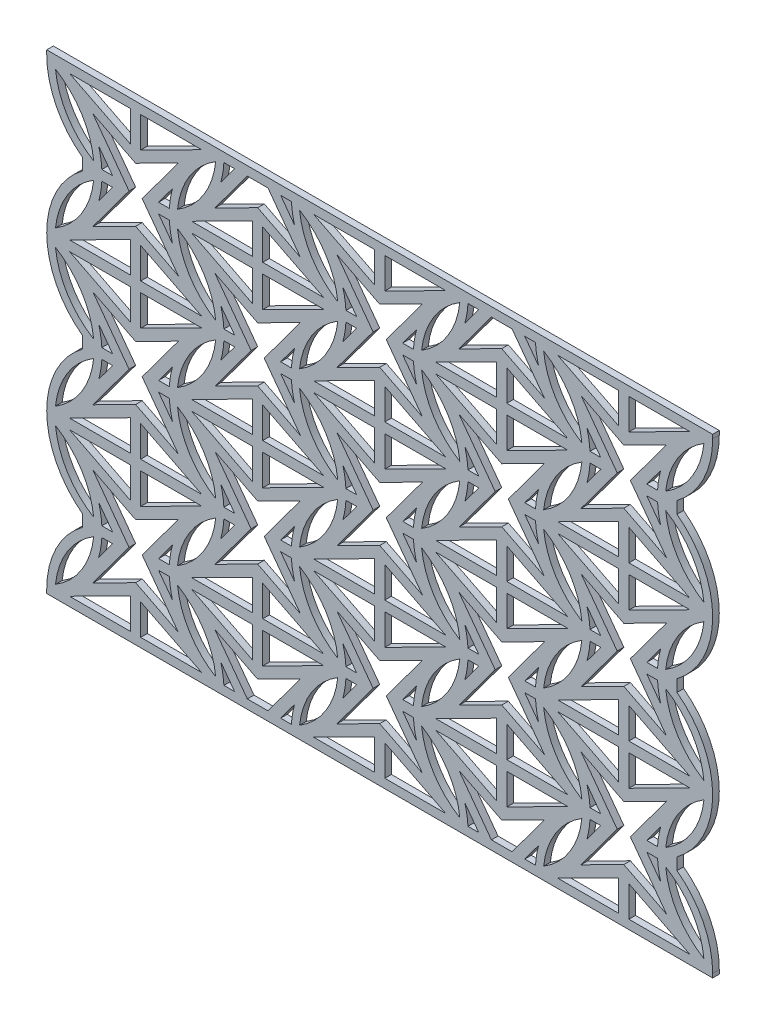
SolidWorks part; units mm, degrees
ref_plane "Front Plane" through (0, 0, 0) normal (0, 0, 1) x (1, 0, 0)
ref_plane "Top Plane" through (0, 0, 0) normal (0, 1, 0) x (1, 0, 0)
ref_plane "Right Plane" through (0, 0, 0) normal (1, 0, 0) x (0, 0, -1)
sketch "Sketch2" plane through (0, 0, 0) normal (0, 0, 1) x (1, 0, 0)
  line L0 (-7.7461, 7.4126) -> (-1.1882, -1.4456)
  line L1 (-0.9234, -14.5032) -> (-11.964, -14.5032)
  line L2 (7.7461, -10.3038) -> (1.1882, -1.4456)
  line L3 (-4.1661, -0.5271) -> (-6.115, -0.5271)
  line L4 (0.9234, 11.4505) -> (0.9234, 11.612)
  line L5 (4.1661, -0.5271) -> (6.115, -0.5271)
  line L6 (-0.9234, 11.612) -> (-11.964, 11.612)
  line L7 (0.9234, -8.927) -> (0.9234, -14.5032)
  line L8 (11.964, 11.612) -> (0.9234, 11.612)
  line L9 (-0.9234, -8.927) -> (-0.9234, -14.3417)
  line L10 (7.7461, 7.4126) -> (1.1882, -1.4456)
  line L11 (0.9234, 6.0358) -> (11.964, 11.612)
  line L12 (-9.6385, -0.3656) -> (-9.6385, -2.5257)
  line L13 (0.9234, -8.927) -> (11.964, -14.5032)
  line L14 (-7.7461, -10.3038) -> (-1.1882, -1.4456)
  line L15 (-4.1661, -2.3642) -> (-6.115, -2.3642)
  line L16 (-0.9234, 6.0358) -> (-11.964, 11.612)
  line L17 (4.1661, -2.3642) -> (6.115, -2.3642)
  line L18 (0, 3.5003) -> (-7.7461, 7.4126)
  line L19 (-16.1, 12.5305) -> (16.1, 12.5305) construction
  line L20 (11.964, -14.5032) -> (0.9234, -14.5032)
  line L21 (0, -6.3916) -> (-7.7461, -10.3038)
  line L22 (-0.9234, 11.4505) -> (-0.9234, 11.612)
  line L23 (-0.9234, -14.3417) -> (-0.9234, -14.5032)
  line L24 (-4.1661, -0.5271) -> (-6.6809, 2.8698)
  line L25 (0.9234, 6.0358) -> (0.9234, 11.4505)
  line L26 (9.6385, -0.3656) -> (9.6385, -2.5257) construction
  line L27 (-0.9234, -8.927) -> (-11.964, -14.5032)
  line L28 (4.1661, -0.5271) -> (6.6809, 2.8698)
  line L29 (4.1661, -2.3642) -> (6.6809, -5.761)
  line L30 (0, -6.3916) -> (7.7461, -10.3038)
  line L31 (-4.1661, -2.3642) -> (-6.6809, -5.761)
  line L32 (-0.9234, 6.0358) -> (-0.9234, 11.4505)
  line L33 (0, 3.5003) -> (7.7461, 7.4126)
  line L34 (-16.1, -15.4218) -> (16.1, -15.4218) construction
  line L35 (-16.1, 12.5305) -> (-16.1, 13.247) construction
  line L36 (-16.1, 13.247) -> (16.1, 13.247) construction
  line L37 (16.1, 13.247) -> (16.1, 12.5305) construction
  line L38 (-16.1, -15.4218) -> (-16.1, -16.1382)
  line L39 (-16.1, -16.1382) -> (16.1, -16.1382)
  line L40 (16.1, -16.1382) -> (16.1, -15.4218) construction
  line L41 (-24.8754, -31.139) -> (-24.8754, -30.9775) construction
  line L42 (-21.6327, -44.9536) -> (-19.6838, -44.9536) construction
  line L43 (-25.7989, -48.981) -> (-18.0527, -52.8933) construction
  line L44 (-41.8989, -30.0589) -> (-41.8989, -29.3425)
  line L45 (-18.0527, -35.1769) -> (-24.6106, -44.0351) construction
  line L46 (-33.545, -52.8933) -> (-26.9871, -44.0351) construction
  line L47 (-9.6989, -29.3425) -> (-9.6989, -30.0589)
  line L48 (-26.7223, -51.5165) -> (-26.7223, -56.9312) construction
  line L49 (-29.965, -44.9536) -> (-31.9139, -44.9536) construction
  line L50 (-41.8989, -58.0112) -> (-41.8989, -58.7277)
  line L51 (-29.965, -43.1165) -> (-32.4798, -39.7197) construction
  line L52 (-41.8989, -58.7277) -> (-9.6989, -58.7277) construction
  line L53 (-33.545, -35.1769) -> (-26.9871, -44.0351) construction
  line L54 (-35.4374, -42.955) -> (-35.4374, -45.1151) construction
  line L55 (-25.7989, -48.981) -> (-33.545, -52.8933) construction
  line L56 (-26.7223, -51.5165) -> (-37.7629, -57.0927) construction
  line L57 (-41.8989, -30.0589) -> (-9.6989, -30.0589) construction
  line L58 (-13.8348, -30.9775) -> (-24.8754, -30.9775) construction
  line L59 (-26.7223, -36.5537) -> (-26.7223, -31.139) construction
  line L60 (-18.0527, -52.8933) -> (-24.6106, -44.0351) construction
  line L61 (-24.8754, -51.5165) -> (-13.8348, -57.0927) construction
  line L62 (-21.6327, -43.1165) -> (-19.1179, -39.7197) construction
  line L63 (-26.7223, -57.0927) -> (-37.7629, -57.0927) construction
  line L64 (-26.7223, -36.5537) -> (-37.7629, -30.9775) construction
  line L65 (-21.6327, -44.9536) -> (-19.1179, -48.3505) construction
  line L66 (-21.6327, -43.1165) -> (-19.6838, -43.1165) construction
  line L67 (-25.7989, -39.0891) -> (-33.545, -35.1769) construction
  line L68 (-29.965, -44.9536) -> (-32.4798, -48.3505) construction
  line L69 (-29.965, -43.1165) -> (-31.9139, -43.1165) construction
  line L70 (-26.7223, -31.139) -> (-26.7223, -30.9775) construction
  line L71 (-41.8989, -29.3425) -> (-9.6989, -29.3425) construction
  line L72 (-26.7223, -30.9775) -> (-37.7629, -30.9775) construction
  line L73 (-26.7223, -56.9312) -> (-26.7223, -57.0927) construction
  line L74 (-9.6989, -58.7277) -> (-9.6989, -58.0112)
  line L75 (-41.8989, -58.0112) -> (-9.6989, -58.0112) construction
  line L76 (-13.8348, -57.0927) -> (-24.8754, -57.0927) construction
  line L77 (-16.1603, -42.955) -> (-16.1603, -45.1151) construction
  line L78 (-24.8754, -51.5165) -> (-24.8754, -57.0927) construction
  line L79 (-24.8754, -36.5537) -> (-24.8754, -31.139) construction
  line L80 (-25.7989, -39.0891) -> (-18.0527, -35.1769) construction
  line L81 (-24.8754, -36.5537) -> (-13.8348, -30.9775) construction
  line L82 (23.0309, -2.5257) -> (23.0309, -2.3642)
  line L83 (26.2736, -16.3403) -> (28.2225, -16.3403) construction
  line L84 (22.1074, -20.3677) -> (29.8536, -24.28) construction
  line L85 (6.0074, -1.4456) -> (6.0074, -0.7292) construction
  line L86 (29.8536, -6.5635) -> (23.9757, -14.5032)
  line L87 (14.3613, -24.28) -> (20.9192, -15.4218) construction
  line L88 (38.2074, -0.7292) -> (38.2074, -1.4456) construction
  line L89 (21.184, -22.9032) -> (21.184, -28.3178) construction
  line L90 (17.9413, -16.3403) -> (15.9924, -16.3403) construction
  line L91 (6.0074, -29.3979) -> (6.0074, -30.1144) construction
  line L92 (17.9413, -14.5032) -> (15.4265, -11.1064)
  line L93 (6.0074, -30.1144) -> (38.2074, -30.1144) construction
  line L94 (14.3613, -6.5635) -> (20.2392, -14.5032)
  line L95 (12.4689, -14.3417) -> (12.4689, -16.5018) construction
  line L96 (22.1074, -20.3677) -> (14.3613, -24.28) construction
  line L97 (21.184, -22.9032) -> (10.1434, -28.4794) construction
  line L98 (6.0074, -1.4456) -> (38.2074, -1.4456) construction
  line L99 (34.0715, -2.3642) -> (23.0309, -2.3642)
  line L100 (21.184, -7.9404) -> (21.184, -2.5257)
  line L101 (29.8536, -24.28) -> (23.2957, -15.4218) construction
  line L102 (23.0309, -22.9032) -> (34.0715, -28.4794) construction
  line L103 (26.2736, -14.5032) -> (28.7884, -11.1064)
  line L104 (21.184, -28.4794) -> (10.1434, -28.4794) construction
  line L105 (21.184, -7.9404) -> (10.1434, -2.3642)
  line L106 (26.2736, -16.3403) -> (28.7884, -19.7372) construction
  line L107 (26.2736, -14.5032) -> (28.2225, -14.5032)
  line L108 (22.1074, -10.4758) -> (14.3613, -6.5635)
  line L109 (17.9413, -16.3403) -> (15.4265, -19.7372) construction
  line L110 (17.9413, -14.5032) -> (15.9924, -14.5032)
  line L111 (21.184, -2.5257) -> (21.184, -2.3642)
  line L112 (6.0074, -0.7292) -> (38.2074, -0.7292) construction
  line L113 (21.184, -2.3642) -> (10.1434, -2.3642)
  line L114 (21.184, -28.3178) -> (21.184, -28.4794) construction
  line L115 (38.2074, -30.1144) -> (38.2074, -29.3979) construction
  line L116 (6.0074, -29.3979) -> (38.2074, -29.3979) construction
  line L117 (34.0715, -28.4794) -> (23.0309, -28.4794) construction
  line L118 (31.746, -14.3417) -> (31.746, -16.5018) construction
  line L119 (23.0309, -22.9032) -> (23.0309, -28.4794) construction
  line L120 (23.0309, -7.9404) -> (23.0309, -2.5257)
  line L121 (22.1074, -10.4758) -> (29.8536, -6.5635)
  line L122 (23.0309, -7.9404) -> (34.0715, -2.3642)
  line L123 (26.2736, 11.612) -> (28.2225, 11.612)
  line L124 (29.8536, 3.6723) -> (23.2957, 12.5305)
  line L125 (23.0309, 5.0491) -> (23.0309, -0.5271)
  line L126 (31.746, 13.6106) -> (31.746, 11.4505) construction
  line L127 (34.0715, 25.5881) -> (23.0309, 25.5881)
  line L128 (38.2074, 27.2231) -> (38.2074, 26.5067) construction
  line L129 (12.4689, 13.6106) -> (12.4689, 11.4505) construction
  line L130 (23.0309, 25.4266) -> (23.0309, 25.5881)
  line L131 (21.184, 5.0491) -> (10.1434, -0.5271)
  line L132 (6.0074, 27.2231) -> (38.2074, 27.2231) construction
  line L133 (23.0309, 5.0491) -> (34.0715, -0.5271)
  line L134 (6.0074, 26.5067) -> (6.0074, 27.2231) construction
  line L135 (6.0074, -1.4456) -> (6.0074, -2.1621) construction
  line L136 (6.0074, -1.4456) -> (38.2074, -1.4456) construction
  line L137 (21.184, 20.0119) -> (10.1434, 25.5881)
  line L138 (23.0309, 20.0119) -> (23.0309, 25.4266)
  line L139 (22.1074, 7.5846) -> (14.3613, 3.6723)
  line L140 (34.0715, -0.5271) -> (23.0309, -0.5271)
  line L141 (17.9413, 13.449) -> (15.9924, 13.449)
  line L142 (23.0309, 20.0119) -> (34.0715, 25.5881)
  line L143 (22.1074, 7.5846) -> (29.8536, 3.6723)
  line L144 (21.184, 20.0119) -> (21.184, 25.4266)
  line L145 (22.1074, 17.4764) -> (29.8536, 21.3887)
  line L146 (26.2736, 13.449) -> (28.2225, 13.449)
  line L147 (17.9413, 13.449) -> (15.4265, 16.8459)
  line L148 (21.184, 25.4266) -> (21.184, 25.5881)
  line L149 (6.0074, 26.5067) -> (38.2074, 26.5067) construction
  line L150 (26.2736, 13.449) -> (28.7884, 16.8459)
  line L151 (38.2074, -2.1621) -> (38.2074, -1.4456) construction
  line L152 (21.184, -0.5271) -> (10.1434, -0.5271)
  line L153 (14.3613, 3.6723) -> (20.9192, 12.5305)
  line L154 (14.3613, 21.3887) -> (20.9192, 12.5305)
  line L155 (21.184, 25.5881) -> (10.1434, 25.5881)
  line L156 (21.184, 5.0491) -> (21.184, -0.3656)
  line L157 (17.9413, 11.612) -> (15.4265, 8.2151)
  line L158 (21.184, -0.3656) -> (21.184, -0.5271)
  line L159 (29.8536, 21.3887) -> (23.2957, 12.5305)
  line L160 (26.2736, 11.612) -> (28.7884, 8.2151)
  line L161 (17.9413, 11.612) -> (15.9924, 11.612)
  line L162 (22.1074, 17.4764) -> (14.3613, 21.3887)
  line L163 (6.0074, -2.1621) -> (38.2074, -2.1621) construction
  line L164 (48.381, -2.3642) -> (50.3299, -2.3642)
  line L165 (51.961, -10.3038) -> (45.4031, -1.4456)
  line L166 (45.1383, -8.927) -> (45.1383, -14.5032)
  line L167 (53.8534, -0.3656) -> (53.8534, -2.5257) construction
  line L168 (56.1789, 11.612) -> (45.1383, 11.612)
  line L169 (60.3149, 13.247) -> (60.3149, 12.5305) construction
  line L170 (34.5764, -0.3656) -> (34.5764, -2.5257) construction
  line L171 (45.1383, 11.4505) -> (45.1383, 11.612)
  line L172 (43.2915, -8.927) -> (32.2509, -14.5032)
  line L173 (28.1149, 13.247) -> (60.3149, 13.247) construction
  line L174 (45.1383, -8.927) -> (56.1789, -14.5032)
  line L175 (28.1149, 12.5305) -> (28.1149, 13.247) construction
  line L176 (28.1149, -15.4218) -> (28.1149, -16.1382) construction
  line L177 (28.1149, -15.4218) -> (60.3149, -15.4218) construction
  line L178 (43.2915, 6.0358) -> (32.2509, 11.612)
  line L179 (45.1383, 6.0358) -> (45.1383, 11.4505)
  line L180 (44.2149, -6.3916) -> (36.4688, -10.3038)
  line L181 (56.1789, -14.5032) -> (45.1383, -14.5032)
  line L182 (40.0488, -0.5271) -> (38.0999, -0.5271)
  line L183 (45.1383, 6.0358) -> (56.1789, 11.612)
  line L184 (44.2149, -6.3916) -> (51.961, -10.3038)
  line L185 (43.2915, 6.0358) -> (43.2915, 11.4505)
  line L186 (44.2149, 3.5003) -> (51.961, 7.4126)
  line L187 (48.381, -0.5271) -> (50.3299, -0.5271)
  line L188 (40.0488, -0.5271) -> (37.534, 2.8698)
  line L189 (43.2915, 11.4505) -> (43.2915, 11.612)
  line L190 (28.1149, 12.5305) -> (60.3149, 12.5305) construction
  line L191 (48.381, -0.5271) -> (50.8958, 2.8698)
  line L192 (60.3149, -16.1382) -> (60.3149, -15.4218) construction
  line L193 (43.2915, -14.5032) -> (32.2509, -14.5032)
  line L194 (36.4688, -10.3038) -> (43.0267, -1.4456)
  line L195 (36.4688, 7.4126) -> (43.0267, -1.4456)
  line L196 (43.2915, 11.612) -> (32.2509, 11.612)
  line L197 (43.2915, -8.927) -> (43.2915, -14.3417)
  line L198 (40.0488, -2.3642) -> (37.534, -5.761)
  line L199 (43.2915, -14.3417) -> (43.2915, -14.5032)
  line L200 (51.961, 7.4126) -> (45.4031, -1.4456)
  line L201 (48.381, -2.3642) -> (50.8958, -5.761)
  line L202 (40.0488, -2.3642) -> (38.0999, -2.3642)
  line L203 (44.2149, 3.5003) -> (36.4688, 7.4126)
  line L204 (28.1149, -16.1382) -> (60.3149, -16.1382)
  line L205 (70.4885, 11.612) -> (72.4374, 11.612)
  line L206 (74.0685, 3.6723) -> (67.5106, 12.5305)
  line L207 (67.2458, 5.0491) -> (67.2458, -0.5271)
  line L208 (75.9609, 13.6106) -> (75.9609, 11.4505) construction
  line L209 (78.2864, 25.5881) -> (67.2458, 25.5881)
  line L210 (82.4223, 27.2231) -> (82.4223, 26.5067) construction
  line L211 (56.6838, 13.6106) -> (56.6838, 11.4505) construction
  line L212 (67.2458, 25.4266) -> (67.2458, 25.5881)
  line L213 (65.3989, 5.0491) -> (54.3583, -0.5271)
  line L214 (50.2223, 27.2231) -> (82.4223, 27.2231) construction
  line L215 (67.2458, 5.0491) -> (78.2864, -0.5271)
  line L216 (50.2223, 26.5067) -> (50.2223, 27.2231) construction
  line L217 (50.2223, -1.4456) -> (50.2223, -2.1621) construction
  line L218 (50.2223, -1.4456) -> (82.4223, -1.4456) construction
  line L219 (65.3989, 20.0119) -> (54.3583, 25.5881)
  line L220 (67.2458, 20.0119) -> (67.2458, 25.4266)
  line L221 (66.3223, 7.5846) -> (58.5762, 3.6723)
  line L222 (78.2864, -0.5271) -> (67.2458, -0.5271)
  line L223 (62.1562, 13.449) -> (60.2073, 13.449)
  line L224 (67.2458, 20.0119) -> (78.2864, 25.5881)
  line L225 (66.3223, 7.5846) -> (74.0685, 3.6723)
  line L226 (65.3989, 20.0119) -> (65.3989, 25.4266)
  line L227 (66.3223, 17.4764) -> (74.0685, 21.3887)
  line L228 (70.4885, 13.449) -> (72.4374, 13.449)
  line L229 (62.1562, 13.449) -> (59.6414, 16.8459)
  line L230 (65.3989, 25.4266) -> (65.3989, 25.5881)
  line L231 (50.2223, 26.5067) -> (82.4223, 26.5067) construction
  line L232 (70.4885, 13.449) -> (73.0033, 16.8459)
  line L233 (82.4223, -2.1621) -> (82.4223, -1.4456) construction
  line L234 (65.3989, -0.5271) -> (54.3583, -0.5271)
  line L235 (58.5762, 3.6723) -> (65.1341, 12.5305)
  line L236 (58.5762, 21.3887) -> (65.1341, 12.5305)
  line L237 (65.3989, 25.5881) -> (54.3583, 25.5881)
  line L238 (65.3989, 5.0491) -> (65.3989, -0.3656)
  line L239 (62.1562, 11.612) -> (59.6414, 8.2151)
  line L240 (65.3989, -0.3656) -> (65.3989, -0.5271)
  line L241 (74.0685, 21.3887) -> (67.5106, 12.5305)
  line L242 (70.4885, 11.612) -> (73.0033, 8.2151)
  line L243 (62.1562, 11.612) -> (60.2073, 11.612)
  line L244 (66.3223, 17.4764) -> (58.5762, 21.3887)
  line L245 (50.2223, -2.1621) -> (82.4223, -2.1621) construction
  line L246 (48.381, 25.5881) -> (50.3299, 25.5881)
  line L247 (51.961, 17.6484) -> (45.4031, 26.5067)
  line L248 (45.1383, 19.0253) -> (45.1383, 13.449)
  line L249 (53.8534, 27.5867) -> (53.8534, 25.4266) construction
  line L250 (56.1789, 39.5643) -> (45.1383, 39.5643)
  line L251 (60.3149, 41.1992) -> (60.3149, 40.4828) construction
  line L252 (34.5764, 27.5867) -> (34.5764, 25.4266) construction
  line L253 (45.1383, 39.4027) -> (45.1383, 39.5643)
  line L254 (43.2915, 19.0253) -> (32.2509, 13.449)
  line L255 (28.1149, 41.1992) -> (60.3149, 41.1992) construction
  line L256 (45.1383, 19.0253) -> (56.1789, 13.449)
  line L257 (28.1149, 40.4828) -> (28.1149, 41.1992) construction
  line L258 (28.1149, 12.5305) -> (28.1149, 11.8141) construction
  line L259 (28.1149, 12.5305) -> (60.3149, 12.5305) construction
  line L260 (43.2915, 33.9881) -> (32.2509, 39.5643)
  line L261 (45.1383, 33.9881) -> (45.1383, 39.4027)
  line L262 (44.2149, 21.5607) -> (36.4688, 17.6484)
  line L263 (56.1789, 13.449) -> (45.1383, 13.449)
  line L264 (40.0488, 27.4252) -> (38.0999, 27.4252)
  line L265 (45.1383, 33.9881) -> (56.1789, 39.5643)
  line L266 (44.2149, 21.5607) -> (51.961, 17.6484)
  line L267 (43.2915, 33.9881) -> (43.2915, 39.4027)
  line L268 (44.2149, 31.4526) -> (51.961, 35.3649)
  line L269 (48.381, 27.4252) -> (50.3299, 27.4252)
  line L270 (40.0488, 27.4252) -> (37.534, 30.8221)
  line L271 (43.2915, 39.4027) -> (43.2915, 39.5643)
  line L272 (28.1149, 40.4828) -> (60.3149, 40.4828) construction
  line L273 (48.381, 27.4252) -> (50.8958, 30.8221)
  line L274 (60.3149, 11.8141) -> (60.3149, 12.5305) construction
  line L275 (43.2915, 13.449) -> (32.2509, 13.449)
  line L276 (36.4688, 17.6484) -> (43.0267, 26.5067)
  line L277 (36.4688, 35.3649) -> (43.0267, 26.5067)
  line L278 (43.2915, 39.5643) -> (32.2509, 39.5643)
  line L279 (43.2915, 19.0253) -> (43.2915, 13.6106)
  line L280 (40.0488, 25.5881) -> (37.534, 22.1912)
  line L281 (43.2915, 13.6106) -> (43.2915, 13.449)
  line L282 (51.961, 35.3649) -> (45.4031, 26.5067)
  line L283 (48.381, 25.5881) -> (50.8958, 22.1912)
  line L284 (40.0488, 25.5881) -> (38.0999, 25.5881)
  line L285 (44.2149, 31.4526) -> (36.4688, 35.3649)
  line L286 (28.1149, 11.8141) -> (60.3149, 11.8141) construction
  line L287 (70.4885, 39.5643) -> (72.4374, 39.5643)
  line L288 (74.0685, 31.6246) -> (67.5106, 40.4828)
  line L289 (67.2458, 33.0014) -> (67.2458, 27.4252)
  line L290 (75.9609, 41.5629) -> (75.9609, 39.4027) construction
  line L291 (78.2864, 53.5404) -> (67.2458, 53.5404)
  line L292 (82.4223, 55.1754) -> (82.4223, 54.4589) construction
  line L293 (56.6838, 41.5629) -> (56.6838, 39.4027) construction
  line L294 (67.2458, 53.3789) -> (67.2458, 53.5404)
  line L295 (65.3989, 33.0014) -> (54.3583, 27.4252)
  line L296 (50.2223, 55.1754) -> (82.4223, 55.1754) construction
  line L297 (67.2458, 33.0014) -> (78.2864, 27.4252)
  line L298 (50.2223, 54.4589) -> (50.2223, 55.1754) construction
  line L299 (50.2223, 26.5067) -> (50.2223, 25.7902) construction
  line L300 (50.2223, 26.5067) -> (82.4223, 26.5067) construction
  line L301 (65.3989, 47.9642) -> (54.3583, 53.5404)
  line L302 (67.2458, 47.9642) -> (67.2458, 53.3789)
  line L303 (66.3223, 35.5369) -> (58.5762, 31.6246)
  line L304 (78.2864, 27.4252) -> (67.2458, 27.4252)
  line L305 (62.1562, 41.4013) -> (60.2073, 41.4013)
  line L306 (67.2458, 47.9642) -> (78.2864, 53.5404)
  line L307 (66.3223, 35.5369) -> (74.0685, 31.6246)
  line L308 (65.3989, 47.9642) -> (65.3989, 53.3789)
  line L309 (66.3223, 45.4287) -> (74.0685, 49.341)
  line L310 (70.4885, 41.4013) -> (72.4374, 41.4013)
  line L311 (62.1562, 41.4013) -> (59.6414, 44.7982)
  line L312 (65.3989, 53.3789) -> (65.3989, 53.5404)
  line L313 (50.2223, 54.4589) -> (82.4223, 54.4589) construction
  line L314 (70.4885, 41.4013) -> (73.0033, 44.7982)
  line L315 (82.4223, 25.7902) -> (82.4223, 26.5067) construction
  line L316 (65.3989, 27.4252) -> (54.3583, 27.4252)
  line L317 (58.5762, 31.6246) -> (65.1341, 40.4828)
  line L318 (58.5762, 49.341) -> (65.1341, 40.4828)
  line L319 (65.3989, 53.5404) -> (54.3583, 53.5404)
  line L320 (65.3989, 33.0014) -> (65.3989, 27.5867)
  line L321 (62.1562, 39.5643) -> (59.6414, 36.1674)
  line L322 (65.3989, 27.5867) -> (65.3989, 27.4252)
  line L323 (74.0685, 49.341) -> (67.5106, 40.4828)
  line L324 (70.4885, 39.5643) -> (73.0033, 36.1674)
  line L325 (62.1562, 39.5643) -> (60.2073, 39.5643)
  line L326 (66.3223, 45.4287) -> (58.5762, 49.341)
  line L327 (50.2223, 25.7902) -> (82.4223, 25.7902) construction
  line L328 (4.1661, 27.4252) -> (6.115, 27.4252)
  line L329 (-16.1, 41.1992) -> (16.1, 41.1992) construction
  line L330 (-0.9234, 19.0253) -> (-11.964, 13.449)
  line L331 (0.9234, 33.9881) -> (0.9234, 39.4027)
  line L332 (-16.1, 12.5305) -> (-16.1, 11.8141) construction
  line L333 (0, 21.5607) -> (-7.7461, 17.6484)
  line L334 (4.1661, 27.4252) -> (6.6809, 30.8221)
  line L335 (11.964, 39.5643) -> (0.9234, 39.5643)
  line L336 (0.9234, 19.0253) -> (0.9234, 13.449)
  line L337 (9.6385, 27.5867) -> (9.6385, 25.4266) construction
  line L338 (7.7461, 35.3649) -> (1.1882, 26.5067)
  line L339 (-4.1661, 25.5881) -> (-6.6809, 22.1912)
  line L340 (0, 31.4526) -> (7.7461, 35.3649)
  line L341 (4.1661, 25.5881) -> (6.115, 25.5881)
  line L342 (-7.7461, 17.6484) -> (-1.1882, 26.5067)
  line L343 (0.9234, 19.0253) -> (11.964, 13.449)
  line L344 (-4.1661, 27.4252) -> (-6.6809, 30.8221)
  line L345 (-0.9234, 33.9881) -> (-11.964, 39.5643)
  line L346 (-16.1, 40.4828) -> (16.1, 40.4828) construction
  line L347 (-7.7461, 35.3649) -> (-1.1882, 26.5067)
  line L348 (0.9234, 33.9881) -> (11.964, 39.5643)
  line L349 (-0.9234, 13.449) -> (-11.964, 13.449)
  line L350 (0.9234, 39.4027) -> (0.9234, 39.5643)
  line L351 (-0.9234, 13.6106) -> (-0.9234, 13.449)
  line L352 (16.1, 41.1992) -> (16.1, 40.4828) construction
  line L353 (7.7461, 17.6484) -> (1.1882, 26.5067)
  line L354 (-16.1, 40.4828) -> (-16.1, 41.1992) construction
  line L355 (4.1661, 25.5881) -> (6.6809, 22.1912)
  line L356 (-16.1, 12.5305) -> (16.1, 12.5305) construction
  line L357 (0, 31.4526) -> (-7.7461, 35.3649)
  line L358 (11.964, 13.449) -> (0.9234, 13.449)
  line L359 (0, 21.5607) -> (7.7461, 17.6484)
  line L360 (-4.1661, 27.4252) -> (-6.115, 27.4252)
  line L361 (-4.1661, 25.5881) -> (-6.115, 25.5881)
  line L362 (-0.9234, 39.4027) -> (-0.9234, 39.5643)
  line L363 (-0.9234, 19.0253) -> (-0.9234, 13.6106)
  line L364 (-0.9234, 39.5643) -> (-11.964, 39.5643)
  line L365 (-9.6385, 27.5867) -> (-9.6385, 25.4266)
  line L366 (16.1, 11.8141) -> (16.1, 12.5305) construction
  line L367 (-0.9234, 33.9881) -> (-0.9234, 39.4027)
  line L368 (-16.1, 11.8141) -> (16.1, 11.8141) construction
  line L369 (26.2736, 41.4013) -> (28.2225, 41.4013)
  line L370 (6.0074, 55.1754) -> (38.2074, 55.1754) construction
  line L371 (21.184, 33.0014) -> (10.1434, 27.4252)
  line L372 (23.0309, 47.9642) -> (23.0309, 53.3789)
  line L373 (6.0074, 26.5067) -> (6.0074, 25.7902) construction
  line L374 (22.1074, 35.5369) -> (14.3613, 31.6246)
  line L375 (26.2736, 41.4013) -> (28.7884, 44.7982)
  line L376 (34.0715, 53.5404) -> (23.0309, 53.5404)
  line L377 (23.0309, 33.0014) -> (23.0309, 27.4252)
  line L378 (31.746, 41.5629) -> (31.746, 39.4027) construction
  line L379 (29.8536, 49.341) -> (23.2957, 40.4828)
  line L380 (17.9413, 39.5643) -> (15.4265, 36.1674)
  line L381 (22.1074, 45.4287) -> (29.8536, 49.341)
  line L382 (26.2736, 39.5643) -> (28.2225, 39.5643)
  line L383 (14.3613, 31.6246) -> (20.9192, 40.4828)
  line L384 (23.0309, 33.0014) -> (34.0715, 27.4252)
  line L385 (17.9413, 41.4013) -> (15.4265, 44.7982)
  line L386 (21.184, 47.9642) -> (10.1434, 53.5404)
  line L387 (6.0074, 54.4589) -> (38.2074, 54.4589) construction
  line L388 (14.3613, 49.341) -> (20.9192, 40.4828)
  line L389 (23.0309, 47.9642) -> (34.0715, 53.5404)
  line L390 (21.184, 27.4252) -> (10.1434, 27.4252)
  line L391 (23.0309, 53.3789) -> (23.0309, 53.5404)
  line L392 (21.184, 27.5867) -> (21.184, 27.4252)
  line L393 (38.2074, 55.1754) -> (38.2074, 54.4589) construction
  line L394 (29.8536, 31.6246) -> (23.2957, 40.4828)
  line L395 (6.0074, 54.4589) -> (6.0074, 55.1754) construction
  line L396 (26.2736, 39.5643) -> (28.7884, 36.1674)
  line L397 (6.0074, 26.5067) -> (38.2074, 26.5067) construction
  line L398 (22.1074, 45.4287) -> (14.3613, 49.341)
  line L399 (34.0715, 27.4252) -> (23.0309, 27.4252)
  line L400 (22.1074, 35.5369) -> (29.8536, 31.6246)
  line L401 (17.9413, 41.4013) -> (15.9924, 41.4013)
  line L402 (17.9413, 39.5643) -> (15.9924, 39.5643)
  line L403 (21.184, 53.3789) -> (21.184, 53.5404)
  line L404 (21.184, 33.0014) -> (21.184, 27.5867)
  line L405 (21.184, 53.5404) -> (10.1434, 53.5404)
  line L406 (12.4689, 41.5629) -> (12.4689, 39.4027) construction
  line L407 (38.2074, 25.7902) -> (38.2074, 26.5067) construction
  line L408 (21.184, 47.9642) -> (21.184, 53.3789)
  line L409 (6.0074, 25.7902) -> (38.2074, 25.7902) construction
  line L410 (48.381, 55.3775) -> (50.3299, 55.3775)
  line L411 (28.1149, 69.1515) -> (60.3149, 69.1515)
  line L412 (43.2915, 46.9775) -> (32.2509, 41.4013)
  line L413 (45.1383, 61.9403) -> (45.1383, 67.355)
  line L414 (28.1149, 40.4828) -> (28.1149, 39.7663) construction
  line L415 (44.2149, 49.513) -> (36.4688, 45.6007)
  line L416 (48.381, 55.3775) -> (50.8958, 58.7743)
  line L417 (56.1789, 67.5165) -> (45.1383, 67.5165)
  line L418 (45.1383, 46.9775) -> (45.1383, 41.4013)
  line L419 (53.8534, 55.539) -> (53.8534, 53.3789) construction
  line L420 (51.961, 63.3172) -> (45.4031, 54.4589)
  line L421 (40.0488, 53.5404) -> (37.534, 50.1435)
  line L422 (44.2149, 59.4049) -> (51.961, 63.3172)
  line L423 (48.381, 53.5404) -> (50.3299, 53.5404)
  line L424 (36.4688, 45.6007) -> (43.0267, 54.4589)
  line L425 (45.1383, 46.9775) -> (56.1789, 41.4013)
  line L426 (40.0488, 55.3775) -> (37.534, 58.7743)
  line L427 (43.2915, 61.9403) -> (32.2509, 67.5165)
  line L428 (28.1149, 68.4351) -> (60.3149, 68.4351) construction
  line L429 (36.4688, 63.3172) -> (43.0267, 54.4589)
  line L430 (45.1383, 61.9403) -> (56.1789, 67.5165)
  line L431 (43.2915, 41.4013) -> (32.2509, 41.4013)
  line L432 (45.1383, 67.355) -> (45.1383, 67.5165)
  line L433 (43.2915, 41.5629) -> (43.2915, 41.4013)
  line L434 (60.3149, 69.1515) -> (60.3149, 68.4351) construction
  line L435 (51.961, 45.6007) -> (45.4031, 54.4589)
  line L436 (28.1149, 68.4351) -> (28.1149, 69.1515) construction
  line L437 (48.381, 53.5404) -> (50.8958, 50.1435)
  line L438 (28.1149, 40.4828) -> (60.3149, 40.4828) construction
  line L439 (44.2149, 59.4049) -> (36.4688, 63.3172)
  line L440 (56.1789, 41.4013) -> (45.1383, 41.4013)
  line L441 (44.2149, 49.513) -> (51.961, 45.6007)
  line L442 (40.0488, 55.3775) -> (38.0999, 55.3775)
  line L443 (40.0488, 53.5404) -> (38.0999, 53.5404)
  line L444 (43.2915, 67.355) -> (43.2915, 67.5165)
  line L445 (43.2915, 46.9775) -> (43.2915, 41.5629)
  line L446 (43.2915, 67.5165) -> (32.2509, 67.5165)
  line L447 (34.5764, 55.539) -> (34.5764, 53.3789) construction
  line L448 (60.3149, 39.7663) -> (60.3149, 40.4828) construction
  line L449 (43.2915, 61.9403) -> (43.2915, 67.355)
  line L450 (28.1149, 39.7663) -> (60.3149, 39.7663) construction
  line L451 (4.1661, 55.3775) -> (6.115, 55.3775)
  line L452 (-16.1, 69.1515) -> (16.1, 69.1515)
  line L453 (-0.9234, 46.9775) -> (-11.964, 41.4013)
  line L454 (0.9234, 61.9403) -> (0.9234, 67.355)
  line L455 (-16.1, 40.4828) -> (-16.1, 39.7663) construction
  line L456 (0, 49.513) -> (-7.7461, 45.6007)
  line L457 (4.1661, 55.3775) -> (6.6809, 58.7743)
  line L458 (11.964, 67.5165) -> (0.9234, 67.5165)
  line L459 (0.9234, 46.9775) -> (0.9234, 41.4013)
  line L460 (9.6385, 55.539) -> (9.6385, 53.3789) construction
  line L461 (7.7461, 63.3172) -> (1.1882, 54.4589)
  line L462 (-4.1661, 53.5404) -> (-6.6809, 50.1435)
  line L463 (0, 59.4049) -> (7.7461, 63.3172)
  line L464 (4.1661, 53.5404) -> (6.115, 53.5404)
  line L465 (-7.7461, 45.6007) -> (-1.1882, 54.4589)
  line L466 (0.9234, 46.9775) -> (11.964, 41.4013)
  line L467 (-4.1661, 55.3775) -> (-6.6809, 58.7743)
  line L468 (-0.9234, 61.9403) -> (-11.964, 67.5165)
  line L469 (-16.1, 68.4351) -> (16.1, 68.4351) construction
  line L470 (-7.7461, 63.3172) -> (-1.1882, 54.4589)
  line L471 (0.9234, 61.9403) -> (11.964, 67.5165)
  line L472 (-0.9234, 41.4013) -> (-11.964, 41.4013)
  line L473 (0.9234, 67.355) -> (0.9234, 67.5165)
  line L474 (-0.9234, 41.5629) -> (-0.9234, 41.4013)
  line L475 (16.1, 69.1515) -> (16.1, 68.4351) construction
  line L476 (7.7461, 45.6007) -> (1.1882, 54.4589)
  line L477 (-16.1, 68.4351) -> (-16.1, 69.1515)
  line L478 (4.1661, 53.5404) -> (6.6809, 50.1435)
  line L479 (-16.1, 40.4828) -> (16.1, 40.4828) construction
  line L480 (0, 59.4049) -> (-7.7461, 63.3172)
  line L481 (11.964, 41.4013) -> (0.9234, 41.4013)
  line L482 (0, 49.513) -> (7.7461, 45.6007)
  line L483 (-4.1661, 55.3775) -> (-6.115, 55.3775)
  line L484 (-4.1661, 53.5404) -> (-6.115, 53.5404)
  line L485 (-0.9234, 67.355) -> (-0.9234, 67.5165)
  line L486 (-0.9234, 46.9775) -> (-0.9234, 41.5629)
  line L487 (-0.9234, 67.5165) -> (-11.964, 67.5165)
  line L488 (-9.6385, 55.539) -> (-9.6385, 53.3789)
  line L489 (16.1, 39.7663) -> (16.1, 40.4828) construction
  line L490 (-0.9234, 61.9403) -> (-0.9234, 67.355)
  line L491 (-16.1, 39.7663) -> (16.1, 39.7663) construction
  line L492 (58.5762, -24.28) -> (65.1341, -15.4218) construction
  line L493 (74.0685, -24.28) -> (67.5106, -15.4218) construction
  line L494 (78.2864, -28.4794) -> (67.2458, -28.4794) construction
  line L495 (62.1562, -16.3403) -> (60.2073, -16.3403) construction
  line L496 (65.3989, -2.5257) -> (65.3989, -2.3642)
  line L497 (67.2458, -7.9404) -> (78.2864, -2.3642)
  line L498 (50.2223, -30.1144) -> (82.4223, -30.1144) construction
  line L499 (50.2223, -29.3979) -> (50.2223, -30.1144) construction
  line L500 (82.4223, -0.7292) -> (82.4223, -1.4456) construction
  line L501 (50.2223, -0.7292) -> (82.4223, -0.7292) construction
  line L502 (66.3223, -20.3677) -> (74.0685, -24.28) construction
  line L503 (65.3989, -28.3178) -> (65.3989, -28.4794) construction
  line L504 (50.2223, -29.3979) -> (82.4223, -29.3979) construction
  line L505 (58.5762, -6.5635) -> (64.4541, -14.5032)
  line L506 (70.4885, -14.5032) -> (73.0033, -11.1064)
  line L507 (65.3989, -22.9032) -> (54.3583, -28.4794) construction
  line L508 (65.3989, -7.9404) -> (54.3583, -2.3642)
  line L509 (70.4885, -16.3403) -> (72.4374, -16.3403) construction
  line L510 (62.1562, -16.3403) -> (59.6414, -19.7372) construction
  line L511 (62.1562, -14.5032) -> (60.2073, -14.5032)
  line L512 (65.3989, -22.9032) -> (65.3989, -28.3178) construction
  line L513 (65.3989, -2.3642) -> (54.3583, -2.3642)
  line L514 (56.6838, -14.3417) -> (56.6838, -16.5018) construction
  line L515 (50.2223, -1.4456) -> (82.4223, -1.4456) construction
  line L516 (62.1562, -14.5032) -> (59.6414, -11.1064)
  line L517 (70.4885, -16.3403) -> (73.0033, -19.7372) construction
  line L518 (66.3223, -10.4758) -> (74.0685, -6.5635)
  line L519 (82.4223, -30.1144) -> (82.4223, -29.3979) construction
  line L520 (74.0685, -6.5635) -> (68.1906, -14.5032)
  line L521 (67.2458, -22.9032) -> (78.2864, -28.4794) construction
  line L522 (67.2458, -7.9404) -> (67.2458, -2.5257)
  line L523 (75.9609, -14.3417) -> (75.9609, -16.5018) construction
  line L524 (66.3223, -20.3677) -> (58.5762, -24.28) construction
  line L525 (65.3989, -28.4794) -> (54.3583, -28.4794) construction
  line L526 (67.2458, -22.9032) -> (67.2458, -28.4794) construction
  line L527 (78.2864, -2.3642) -> (67.2458, -2.3642)
  line L528 (70.4885, -14.5032) -> (72.4374, -14.5032)
  line L529 (67.2458, -2.5257) -> (67.2458, -2.3642)
  line L530 (65.3989, -7.9404) -> (65.3989, -2.5257)
  line L531 (66.3223, -10.4758) -> (58.5762, -6.5635)
  line L532 (50.2223, -1.4456) -> (50.2223, -0.7292) construction
  line L533 (80.6837, -10.3038) -> (87.2416, -1.4456)
  line L534 (96.1759, -10.3038) -> (89.618, -1.4456)
  line L535 (100.3938, -14.5032) -> (89.3532, -14.5032)
  line L536 (84.2637, -2.3642) -> (82.3148, -2.3642)
  line L537 (87.5064, 11.4505) -> (87.5064, 11.612)
  line L538 (89.3532, 6.0358) -> (100.3938, 11.612)
  line L539 (72.3298, -16.1382) -> (104.5298, -16.1382)
  line L540 (72.3298, -15.4218) -> (72.3298, -16.1382) construction
  line L541 (104.5298, 13.247) -> (104.5298, 12.5305) construction
  line L542 (72.3298, 13.247) -> (104.5298, 13.247) construction
  line L543 (88.4298, -6.3916) -> (96.1759, -10.3038)
  line L544 (87.5064, -14.3417) -> (87.5064, -14.5032)
  line L545 (72.3298, -15.4218) -> (104.5298, -15.4218) construction
  line L546 (80.6837, 7.4126) -> (87.2416, -1.4456)
  line L547 (92.5959, -0.5271) -> (95.1107, 2.8698)
  line L548 (87.5064, -8.927) -> (76.4658, -14.5032)
  line L549 (87.5064, 6.0358) -> (76.4658, 11.612)
  line L550 (92.5959, -2.3642) -> (94.5448, -2.3642)
  line L551 (84.2637, -2.3642) -> (81.7489, -5.761)
  line L552 (84.2637, -0.5271) -> (82.3148, -0.5271)
  line L553 (87.5064, -8.927) -> (87.5064, -14.3417)
  line L554 (87.5064, 11.612) -> (76.4658, 11.612)
  line L555 (78.7913, -0.3656) -> (78.7913, -2.5257) construction
  line L556 (72.3298, 12.5305) -> (104.5298, 12.5305) construction
  line L557 (84.2637, -0.5271) -> (81.7489, 2.8698)
  line L558 (92.5959, -2.3642) -> (95.1107, -5.761)
  line L559 (88.4298, 3.5003) -> (96.1759, 7.4126)
  line L560 (104.5298, -16.1382) -> (104.5298, -15.4218)
  line L561 (96.1759, 7.4126) -> (89.618, -1.4456)
  line L562 (89.3532, -8.927) -> (100.3938, -14.5032)
  line L563 (89.3532, 6.0358) -> (89.3532, 11.4505)
  line L564 (98.0683, -0.3656) -> (98.0683, -2.5257)
  line L565 (88.4298, -6.3916) -> (80.6837, -10.3038)
  line L566 (87.5064, -14.5032) -> (76.4658, -14.5032)
  line L567 (89.3532, -8.927) -> (89.3532, -14.5032)
  line L568 (100.3938, 11.612) -> (89.3532, 11.612)
  line L569 (92.5959, -0.5271) -> (94.5448, -0.5271)
  line L570 (89.3532, 11.4505) -> (89.3532, 11.612)
  line L571 (87.5064, 6.0358) -> (87.5064, 11.4505)
  line L572 (88.4298, 3.5003) -> (80.6837, 7.4126)
  line L573 (72.3298, 12.5305) -> (72.3298, 13.247) construction
  line L574 (80.6837, 17.6484) -> (87.2416, 26.5067)
  line L575 (96.1759, 17.6484) -> (89.618, 26.5067)
  line L576 (100.3938, 13.449) -> (89.3532, 13.449)
  line L577 (84.2637, 25.5881) -> (82.3148, 25.5881)
  line L578 (87.5064, 39.4027) -> (87.5064, 39.5643)
  line L579 (89.3532, 33.9881) -> (100.3938, 39.5643)
  line L580 (72.3298, 11.8141) -> (104.5298, 11.8141) construction
  line L581 (72.3298, 12.5305) -> (72.3298, 11.8141) construction
  line L582 (104.5298, 41.1992) -> (104.5298, 40.4828) construction
  line L583 (72.3298, 41.1992) -> (104.5298, 41.1992) construction
  line L584 (88.4298, 21.5607) -> (96.1759, 17.6484)
  line L585 (87.5064, 13.6106) -> (87.5064, 13.449)
  line L586 (72.3298, 12.5305) -> (104.5298, 12.5305) construction
  line L587 (80.6837, 35.3649) -> (87.2416, 26.5067)
  line L588 (92.5959, 27.4252) -> (95.1107, 30.8221)
  line L589 (87.5064, 19.0253) -> (76.4658, 13.449)
  line L590 (87.5064, 33.9881) -> (76.4658, 39.5643)
  line L591 (92.5959, 25.5881) -> (94.5448, 25.5881)
  line L592 (84.2637, 25.5881) -> (81.7489, 22.1912)
  line L593 (84.2637, 27.4252) -> (82.3148, 27.4252)
  line L594 (87.5064, 19.0253) -> (87.5064, 13.6106)
  line L595 (87.5064, 39.5643) -> (76.4658, 39.5643)
  line L596 (78.7913, 27.5867) -> (78.7913, 25.4266) construction
  line L597 (72.3298, 40.4828) -> (104.5298, 40.4828) construction
  line L598 (84.2637, 27.4252) -> (81.7489, 30.8221)
  line L599 (92.5959, 25.5881) -> (95.1107, 22.1912)
  line L600 (88.4298, 31.4526) -> (96.1759, 35.3649)
  line L601 (104.5298, 11.8141) -> (104.5298, 12.5305) construction
  line L602 (96.1759, 35.3649) -> (89.618, 26.5067)
  line L603 (89.3532, 19.0253) -> (100.3938, 13.449)
  line L604 (89.3532, 33.9881) -> (89.3532, 39.4027)
  line L605 (98.0683, 27.5867) -> (98.0683, 25.4266)
  line L606 (88.4298, 21.5607) -> (80.6837, 17.6484)
  line L607 (87.5064, 13.449) -> (76.4658, 13.449)
  line L608 (89.3532, 19.0253) -> (89.3532, 13.449)
  line L609 (100.3938, 39.5643) -> (89.3532, 39.5643)
  line L610 (92.5959, 27.4252) -> (94.5448, 27.4252)
  line L611 (89.3532, 39.4027) -> (89.3532, 39.5643)
  line L612 (87.5064, 33.9881) -> (87.5064, 39.4027)
  line L613 (88.4298, 31.4526) -> (80.6837, 35.3649)
  line L614 (72.3298, 40.4828) -> (72.3298, 41.1992) construction
  line L615 (100.3938, 67.5165) -> (89.3532, 67.5165)
  line L616 (87.5064, 41.5629) -> (87.5064, 41.4013)
  line L617 (78.7913, 55.539) -> (78.7913, 53.3789) construction
  line L618 (88.4298, 49.513) -> (96.1759, 45.6007)
  line L619 (92.5959, 55.3775) -> (94.5448, 55.3775)
  line L620 (89.3532, 46.9775) -> (89.3532, 41.4013)
  line L621 (84.2637, 53.5404) -> (82.3148, 53.5404)
  line L622 (89.3532, 46.9775) -> (100.3938, 41.4013)
  line L623 (72.3298, 68.4351) -> (72.3298, 69.1515) construction
  line L624 (84.2637, 55.3775) -> (81.7489, 58.7743)
  line L625 (87.5064, 41.4013) -> (76.4658, 41.4013)
  line L626 (89.3532, 61.9403) -> (100.3938, 67.5165)
  line L627 (72.3298, 68.4351) -> (104.5298, 68.4351) construction
  line L628 (80.6837, 63.3172) -> (87.2416, 54.4589)
  line L629 (104.5298, 39.7663) -> (104.5298, 40.4828) construction
  line L630 (88.4298, 49.513) -> (80.6837, 45.6007)
  line L631 (72.3298, 39.7663) -> (104.5298, 39.7663) construction
  line L632 (87.5064, 61.9403) -> (76.4658, 67.5165)
  line L633 (84.2637, 53.5404) -> (81.7489, 50.1435)
  line L634 (98.0683, 55.539) -> (98.0683, 53.3789)
  line L635 (87.5064, 61.9403) -> (87.5064, 67.355)
  line L636 (87.5064, 67.5165) -> (76.4658, 67.5165)
  line L637 (104.5298, 69.1515) -> (104.5298, 68.4351)
  line L638 (89.3532, 67.355) -> (89.3532, 67.5165)
  line L639 (88.4298, 59.4049) -> (80.6837, 63.3172)
  line L640 (100.3938, 41.4013) -> (89.3532, 41.4013)
  line L641 (96.1759, 63.3172) -> (89.618, 54.4589)
  line L642 (87.5064, 46.9775) -> (76.4658, 41.4013)
  line L643 (87.5064, 46.9775) -> (87.5064, 41.5629)
  line L644 (87.5064, 67.355) -> (87.5064, 67.5165)
  line L645 (72.3298, 40.4828) -> (72.3298, 39.7663) construction
  line L646 (80.6837, 45.6007) -> (87.2416, 54.4589)
  line L647 (89.3532, 61.9403) -> (89.3532, 67.355)
  line L648 (72.3298, 40.4828) -> (104.5298, 40.4828) construction
  line L649 (96.1759, 45.6007) -> (89.618, 54.4589)
  line L650 (92.5959, 53.5404) -> (94.5448, 53.5404)
  line L651 (92.5959, 55.3775) -> (95.1107, 58.7743)
  line L652 (72.3298, 69.1515) -> (104.5298, 69.1515)
  line L653 (92.5959, 53.5404) -> (95.1107, 50.1435)
  line L654 (88.4298, 59.4049) -> (96.1759, 63.3172)
  line L655 (84.2637, 55.3775) -> (82.3148, 55.3775)
  line L656 (34.0715, 81.4927) -> (23.0309, 81.4927) construction
  line L657 (21.184, 55.539) -> (21.184, 55.3775)
  line L658 (12.4689, 69.5151) -> (12.4689, 67.355) construction
  line L659 (22.1074, 63.4891) -> (29.8536, 59.5769)
  line L660 (26.2736, 69.3536) -> (28.2225, 69.3536) construction
  line L661 (23.0309, 60.9537) -> (23.0309, 55.3775)
  line L662 (17.9413, 67.5165) -> (15.9924, 67.5165)
  line L663 (23.0309, 60.9537) -> (34.0715, 55.3775)
  line L664 (6.0074, 82.4112) -> (6.0074, 83.1277) construction
  line L665 (17.9413, 69.3536) -> (15.4265, 72.7505) construction
  line L666 (21.184, 55.3775) -> (10.1434, 55.3775)
  line L667 (23.0309, 75.9165) -> (34.0715, 81.4927) construction
  line L668 (6.0074, 82.4112) -> (38.2074, 82.4112) construction
  line L669 (14.3613, 77.2933) -> (20.9192, 68.4351) construction
  line L670 (38.2074, 53.7425) -> (38.2074, 54.4589) construction
  line L671 (22.1074, 63.4891) -> (14.3613, 59.5769)
  line L672 (6.0074, 53.7425) -> (38.2074, 53.7425) construction
  line L673 (21.184, 75.9165) -> (10.1434, 81.4927) construction
  line L674 (17.9413, 67.5165) -> (15.4265, 64.1197)
  line L675 (31.746, 69.5151) -> (31.746, 67.355) construction
  line L676 (21.184, 75.9165) -> (21.184, 81.3312) construction
  line L677 (21.184, 81.4927) -> (10.1434, 81.4927) construction
  line L678 (38.2074, 83.1277) -> (38.2074, 82.4112) construction
  line L679 (23.0309, 81.3312) -> (23.0309, 81.4927) construction
  line L680 (22.1074, 73.381) -> (14.3613, 77.2933) construction
  line L681 (34.0715, 55.3775) -> (23.0309, 55.3775)
  line L682 (29.8536, 77.2933) -> (23.2957, 68.4351) construction
  line L683 (21.184, 60.9537) -> (10.1434, 55.3775)
  line L684 (21.184, 60.9537) -> (21.184, 55.539)
  line L685 (21.184, 81.3312) -> (21.184, 81.4927) construction
  line L686 (6.0074, 54.4589) -> (6.0074, 53.7425) construction
  line L687 (14.3613, 59.5769) -> (20.2392, 67.5165)
  line L688 (23.0309, 75.9165) -> (23.0309, 81.3312) construction
  line L689 (6.0074, 54.4589) -> (38.2074, 54.4589) construction
  line L690 (29.8536, 59.5769) -> (23.9757, 67.5165)
  line L691 (26.2736, 67.5165) -> (28.2225, 67.5165)
  line L692 (26.2736, 69.3536) -> (28.7884, 72.7505) construction
  line L693 (6.0074, 83.1277) -> (38.2074, 83.1277) construction
  line L694 (26.2736, 67.5165) -> (28.7884, 64.1197)
  line L695 (22.1074, 73.381) -> (29.8536, 77.2933) construction
  line L696 (17.9413, 69.3536) -> (15.9924, 69.3536) construction
  line L697 (78.2864, 81.4927) -> (67.2458, 81.4927) construction
  line L698 (65.3989, 55.539) -> (65.3989, 55.3775)
  line L699 (56.6838, 69.5151) -> (56.6838, 67.355) construction
  line L700 (66.3223, 63.4891) -> (74.0685, 59.5769)
  line L701 (70.4885, 69.3536) -> (72.4374, 69.3536) construction
  line L702 (67.2458, 60.9537) -> (67.2458, 55.3775)
  line L703 (62.1562, 67.5165) -> (60.2073, 67.5165)
  line L704 (67.2458, 60.9537) -> (78.2864, 55.3775)
  line L705 (50.2223, 82.4112) -> (50.2223, 83.1277) construction
  line L706 (62.1562, 69.3536) -> (59.6414, 72.7505) construction
  line L707 (65.3989, 55.3775) -> (54.3583, 55.3775)
  line L708 (67.2458, 75.9165) -> (78.2864, 81.4927) construction
  line L709 (50.2223, 82.4112) -> (82.4223, 82.4112) construction
  line L710 (58.5762, 77.2933) -> (65.1341, 68.4351) construction
  line L711 (82.4223, 53.7425) -> (82.4223, 54.4589) construction
  line L712 (66.3223, 63.4891) -> (58.5762, 59.5769)
  line L713 (50.2223, 53.7425) -> (82.4223, 53.7425) construction
  line L714 (65.3989, 75.9165) -> (54.3583, 81.4927) construction
  line L715 (62.1562, 67.5165) -> (59.6414, 64.1197)
  line L716 (75.9609, 69.5151) -> (75.9609, 67.355) construction
  line L717 (65.3989, 75.9165) -> (65.3989, 81.3312) construction
  line L718 (65.3989, 81.4927) -> (54.3583, 81.4927) construction
  line L719 (82.4223, 83.1277) -> (82.4223, 82.4112) construction
  line L720 (67.2458, 81.3312) -> (67.2458, 81.4927) construction
  line L721 (66.3223, 73.381) -> (58.5762, 77.2933) construction
  line L722 (78.2864, 55.3775) -> (67.2458, 55.3775)
  line L723 (74.0685, 77.2933) -> (67.5106, 68.4351) construction
  line L724 (65.3989, 60.9537) -> (54.3583, 55.3775)
  line L725 (65.3989, 60.9537) -> (65.3989, 55.539)
  line L726 (65.3989, 81.3312) -> (65.3989, 81.4927) construction
  line L727 (50.2223, 54.4589) -> (50.2223, 53.7425) construction
  line L728 (58.5762, 59.5769) -> (64.4541, 67.5165)
  line L729 (67.2458, 75.9165) -> (67.2458, 81.3312) construction
  line L730 (50.2223, 54.4589) -> (82.4223, 54.4589) construction
  line L731 (74.0685, 59.5769) -> (68.1906, 67.5165)
  line L732 (70.4885, 67.5165) -> (72.4374, 67.5165)
  line L733 (70.4885, 69.3536) -> (73.0033, 72.7505) construction
  line L734 (50.2223, 83.1277) -> (82.4223, 83.1277) construction
  line L735 (70.4885, 67.5165) -> (73.0033, 64.1197)
  line L736 (66.3223, 73.381) -> (74.0685, 77.2933) construction
  line L737 (62.1562, 69.3536) -> (60.2073, 69.3536) construction
  line L738 (16.1, 69.1515) -> (28.1149, 69.1515)
  line L739 (60.3149, 69.1515) -> (72.3298, 69.1515)
  line L740 (16.1, -16.1382) -> (28.1149, -16.1382)
  line L741 (60.3149, -16.1382) -> (72.3298, -16.1382)
  line L742 (20.2392, -14.5032) -> (23.9757, -14.5032)
  line L744 (20.2392, 67.5165) -> (23.9757, 67.5165)
  line L745 (64.4541, 67.5165) -> (68.1906, 67.5165)
  line L747 (64.4541, -14.5032) -> (68.1906, -14.5032)
  arc A0 (14.5125, 11.0136) -> (7.5949, 0.0713) centre (22.1074, -1.4456) ccw
  arc A1 (-7.5949, 0.0713) -> (-14.5125, 11.0136) centre (0, 12.5305) cw
  arc A2 (16.1, 12.5305) -> (9.6385, -0.3656) centre (0, 12.5305) cw construction
  arc A3 (-6.115, -2.3642) -> (-6.6809, -5.761) centre (-22.1074, -1.4456) cw
  arc A4 (6.115, -0.5271) -> (6.6809, 2.8698) centre (22.1074, -1.4456) cw
  arc A5 (-16.1, 12.5305) -> (-9.6385, -0.3656) centre (0, 12.5305) ccw
  arc A6 (9.6385, -2.5257) -> (16.1, -15.4218) centre (0, -15.4218) cw construction
  arc A7 (14.5125, -13.9048) -> (7.5949, -2.9626) centre (22.1074, -1.4456) cw
  arc A8 (-14.5125, 11.0136) -> (-7.5949, 0.0713) centre (-22.1074, -1.4456) cw
  arc A9 (7.5949, 0.0713) -> (14.5125, 11.0136) centre (0, 12.5305) ccw
  arc A10 (-7.5949, -2.9626) -> (-14.5125, -13.9048) centre (0, -15.4218) ccw
  arc A11 (-6.115, -0.5271) -> (-6.6809, 2.8698) centre (-22.1074, -1.4456) ccw
  arc A12 (7.5949, -2.9626) -> (14.5125, -13.9048) centre (0, -15.4218) cw
  arc A13 (6.115, -2.3642) -> (6.6809, -5.761) centre (22.1074, -1.4456) ccw
  arc A14 (-9.6385, -2.5257) -> (-16.1, -15.4218) centre (0, -15.4218) ccw
  arc A15 (-14.5125, -13.9048) -> (-7.5949, -2.9626) centre (-22.1074, -1.4456) ccw
  arc A16 (-31.9139, -44.9536) -> (-32.4798, -48.3505) centre (-47.9063, -44.0351) cw construction
  arc A17 (-18.2039, -45.552) -> (-11.2863, -56.4943) centre (-25.7989, -58.0112) cw construction
  arc A18 (-40.3114, -56.4943) -> (-33.3938, -45.552) centre (-47.9063, -44.0351) ccw construction
  arc A19 (-18.2039, -42.5181) -> (-11.2863, -31.5759) centre (-25.7989, -30.0589) ccw construction
  arc A20 (-9.6989, -30.0589) -> (-16.1603, -42.955) centre (-25.7989, -30.0589) cw construction
  arc A21 (-41.8989, -30.0589) -> (-35.4374, -42.955) centre (-25.7989, -30.0589) ccw construction
  arc A22 (-40.3114, -31.5759) -> (-33.3938, -42.5181) centre (-47.9063, -44.0351) cw construction
  arc A23 (-33.3938, -45.552) -> (-40.3114, -56.4943) centre (-25.7989, -58.0112) ccw construction
  arc A24 (-11.2863, -56.4943) -> (-18.2039, -45.552) centre (-3.6914, -44.0351) cw construction
  arc A25 (-31.9139, -43.1165) -> (-32.4798, -39.7197) centre (-47.9063, -44.0351) ccw construction
  arc A26 (-16.1603, -45.1151) -> (-9.6989, -58.0112) centre (-25.7989, -58.0112) cw construction
  arc A27 (-33.3938, -42.5181) -> (-40.3114, -31.5759) centre (-25.7989, -30.0589) cw construction
  arc A28 (-19.6838, -44.9536) -> (-19.1179, -48.3505) centre (-3.6914, -44.0351) ccw construction
  arc A29 (-19.6838, -43.1165) -> (-19.1179, -39.7197) centre (-3.6914, -44.0351) cw construction
  arc A30 (-35.4374, -45.1151) -> (-41.8989, -58.0112) centre (-25.7989, -58.0112) ccw construction
  arc A31 (-11.2863, -31.5759) -> (-18.2039, -42.5181) centre (-3.6914, -44.0351) ccw construction
  arc A32 (15.9924, -16.3403) -> (15.4265, -19.7372) centre (0, -15.4218) cw construction
  arc A33 (29.7024, -16.9387) -> (36.62, -27.881) centre (22.1074, -29.3979) cw construction
  arc A34 (7.5949, -27.881) -> (14.5125, -16.9387) centre (0, -15.4218) ccw construction
  arc A35 (29.7024, -13.9048) -> (36.62, -2.9626) centre (22.1074, -1.4456) ccw
  arc A36 (38.2074, -1.4456) -> (31.746, -14.3417) centre (22.1074, -1.4456) cw construction
  arc A37 (6.0074, -1.4456) -> (12.4689, -14.3417) centre (22.1074, -1.4456) ccw construction
  arc A39 (14.5125, -16.9387) -> (7.5949, -27.881) centre (22.1074, -29.3979) ccw construction
  arc A40 (36.62, -27.881) -> (29.7024, -16.9387) centre (44.2149, -15.4218) cw construction
  arc A41 (15.9924, -14.5032) -> (15.4265, -11.1064) centre (0, -15.4218) ccw
  arc A42 (31.746, -16.5018) -> (38.2074, -29.3979) centre (22.1074, -29.3979) cw construction
  arc A44 (28.2225, -16.3403) -> (28.7884, -19.7372) centre (44.2149, -15.4218) ccw construction
  arc A45 (28.2225, -14.5032) -> (28.7884, -11.1064) centre (44.2149, -15.4218) cw
  arc A46 (12.4689, -16.5018) -> (6.0074, -29.3979) centre (22.1074, -29.3979) ccw construction
  arc A47 (36.62, -2.9626) -> (29.7024, -13.9048) centre (44.2149, -15.4218) ccw
  arc A48 (36.62, 24.9897) -> (29.7024, 14.0475) centre (44.2149, 12.5305) ccw
  arc A49 (15.9924, 11.612) -> (15.4265, 8.2151) centre (0, 12.5305) cw
  arc A52 (38.2074, 26.5067) -> (31.746, 13.6106) centre (22.1074, 26.5067) cw construction
  arc A55 (28.2225, 13.449) -> (28.7884, 16.8459) centre (44.2149, 12.5305) cw
  arc A56 (6.0074, 26.5067) -> (12.4689, 13.6106) centre (22.1074, 26.5067) ccw construction
  arc A57 (15.9924, 13.449) -> (15.4265, 16.8459) centre (0, 12.5305) ccw
  arc A58 (28.2225, 11.612) -> (28.7884, 8.2151) centre (44.2149, 12.5305) ccw
  arc A59 (29.7024, 14.0475) -> (36.62, 24.9897) centre (22.1074, 26.5067) ccw
  arc A60 (12.4689, 11.4505) -> (6.0074, -1.4456) centre (22.1074, -1.4456) ccw construction
  arc A61 (31.746, 11.4505) -> (38.2074, -1.4456) centre (22.1074, -1.4456) cw construction
  arc A62 (29.7024, 11.0136) -> (36.62, 0.0713) centre (22.1074, -1.4456) cw
  arc A63 (36.62, 0.0713) -> (29.7024, 11.0136) centre (44.2149, 12.5305) cw
  arc A64 (58.7274, 11.0136) -> (51.8098, 0.0713) centre (66.3223, -1.4456) ccw
  arc A65 (38.0999, -2.3642) -> (37.534, -5.761) centre (22.1074, -1.4456) cw
  arc A68 (60.3149, 12.5305) -> (53.8534, -0.3656) centre (44.2149, 12.5305) cw construction
  arc A71 (50.3299, -0.5271) -> (50.8958, 2.8698) centre (66.3223, -1.4456) cw
  arc A72 (28.1149, 12.5305) -> (34.5764, -0.3656) centre (44.2149, 12.5305) ccw construction
  arc A73 (38.0999, -0.5271) -> (37.534, 2.8698) centre (22.1074, -1.4456) ccw
  arc A74 (50.3299, -2.3642) -> (50.8958, -5.761) centre (66.3223, -1.4456) ccw
  arc A75 (51.8098, 0.0713) -> (58.7274, 11.0136) centre (44.2149, 12.5305) ccw
  arc A76 (34.5764, -2.5257) -> (28.1149, -15.4218) centre (44.2149, -15.4218) ccw construction
  arc A77 (53.8534, -2.5257) -> (60.3149, -15.4218) centre (44.2149, -15.4218) cw construction
  arc A78 (51.8098, -2.9626) -> (58.7274, -13.9048) centre (44.2149, -15.4218) cw
  arc A79 (58.7274, -13.9048) -> (51.8098, -2.9626) centre (66.3223, -1.4456) cw
  arc A80 (80.8349, 24.9897) -> (73.9173, 14.0475) centre (88.4298, 12.5305) ccw
  arc A81 (60.2073, 11.612) -> (59.6414, 8.2151) centre (44.2149, 12.5305) cw
  arc A84 (82.4223, 26.5067) -> (75.9609, 13.6106) centre (66.3223, 26.5067) cw construction
  arc A87 (72.4374, 13.449) -> (73.0033, 16.8459) centre (88.4298, 12.5305) cw
  arc A88 (50.2223, 26.5067) -> (56.6838, 13.6106) centre (66.3223, 26.5067) ccw construction
  arc A89 (60.2073, 13.449) -> (59.6414, 16.8459) centre (44.2149, 12.5305) ccw
  arc A90 (72.4374, 11.612) -> (73.0033, 8.2151) centre (88.4298, 12.5305) ccw
  arc A91 (73.9173, 14.0475) -> (80.8349, 24.9897) centre (66.3223, 26.5067) ccw
  arc A92 (56.6838, 11.4505) -> (50.2223, -1.4456) centre (66.3223, -1.4456) ccw construction
  arc A93 (75.9609, 11.4505) -> (82.4223, -1.4456) centre (66.3223, -1.4456) cw construction
  arc A94 (73.9173, 11.0136) -> (80.8349, 0.0713) centre (66.3223, -1.4456) cw
  arc A95 (80.8349, 0.0713) -> (73.9173, 11.0136) centre (88.4298, 12.5305) cw
  arc A96 (58.7274, 38.9659) -> (51.8098, 28.0236) centre (66.3223, 26.5067) ccw
  arc A97 (38.0999, 25.5881) -> (37.534, 22.1912) centre (22.1074, 26.5067) cw
  arc A100 (60.3149, 40.4828) -> (53.8534, 27.5867) centre (44.2149, 40.4828) cw construction
  arc A103 (50.3299, 27.4252) -> (50.8958, 30.8221) centre (66.3223, 26.5067) cw
  arc A104 (28.1149, 40.4828) -> (34.5764, 27.5867) centre (44.2149, 40.4828) ccw construction
  arc A105 (38.0999, 27.4252) -> (37.534, 30.8221) centre (22.1074, 26.5067) ccw
  arc A106 (50.3299, 25.5881) -> (50.8958, 22.1912) centre (66.3223, 26.5067) ccw
  arc A107 (51.8098, 28.0236) -> (58.7274, 38.9659) centre (44.2149, 40.4828) ccw
  arc A108 (34.5764, 25.4266) -> (28.1149, 12.5305) centre (44.2149, 12.5305) ccw construction
  arc A109 (53.8534, 25.4266) -> (60.3149, 12.5305) centre (44.2149, 12.5305) cw construction
  arc A110 (51.8098, 24.9897) -> (58.7274, 14.0475) centre (44.2149, 12.5305) cw
  arc A111 (58.7274, 14.0475) -> (51.8098, 24.9897) centre (66.3223, 26.5067) cw
  arc A112 (80.8349, 52.942) -> (73.9173, 41.9997) centre (88.4298, 40.4828) ccw
  arc A113 (60.2073, 39.5643) -> (59.6414, 36.1674) centre (44.2149, 40.4828) cw
  arc A116 (82.4223, 54.4589) -> (75.9609, 41.5629) centre (66.3223, 54.4589) cw construction
  arc A119 (72.4374, 41.4013) -> (73.0033, 44.7982) centre (88.4298, 40.4828) cw
  arc A120 (50.2223, 54.4589) -> (56.6838, 41.5629) centre (66.3223, 54.4589) ccw construction
  arc A121 (60.2073, 41.4013) -> (59.6414, 44.7982) centre (44.2149, 40.4828) ccw
  arc A122 (72.4374, 39.5643) -> (73.0033, 36.1674) centre (88.4298, 40.4828) ccw
  arc A123 (73.9173, 41.9997) -> (80.8349, 52.942) centre (66.3223, 54.4589) ccw
  arc A124 (56.6838, 39.4027) -> (50.2223, 26.5067) centre (66.3223, 26.5067) ccw construction
  arc A125 (75.9609, 39.4027) -> (82.4223, 26.5067) centre (66.3223, 26.5067) cw construction
  arc A126 (73.9173, 38.9659) -> (80.8349, 28.0236) centre (66.3223, 26.5067) cw
  arc A127 (80.8349, 28.0236) -> (73.9173, 38.9659) centre (88.4298, 40.4828) cw
  arc A128 (-7.5949, 28.0236) -> (-14.5125, 38.9659) centre (0, 40.4828) cw
  arc A129 (-16.1, 40.4828) -> (-9.6385, 27.5867) centre (0, 40.4828) ccw
  arc A130 (6.115, 27.4252) -> (6.6809, 30.8221) centre (22.1074, 26.5067) cw
  arc A131 (16.1, 40.4828) -> (9.6385, 27.5867) centre (0, 40.4828) cw construction
  arc A132 (-6.115, 25.5881) -> (-6.6809, 22.1912) centre (-22.1074, 26.5067) cw
  arc A133 (-6.115, 27.4252) -> (-6.6809, 30.8221) centre (-22.1074, 26.5067) ccw
  arc A134 (7.5949, 28.0236) -> (14.5125, 38.9659) centre (0, 40.4828) ccw
  arc A135 (14.5125, 38.9659) -> (7.5949, 28.0236) centre (22.1074, 26.5067) ccw
  arc A136 (14.5125, 14.0475) -> (7.5949, 24.9897) centre (22.1074, 26.5067) cw
  arc A137 (6.115, 25.5881) -> (6.6809, 22.1912) centre (22.1074, 26.5067) ccw
  arc A138 (-14.5125, 14.0475) -> (-7.5949, 24.9897) centre (-22.1074, 26.5067) ccw
  arc A139 (9.6385, 25.4266) -> (16.1, 12.5305) centre (0, 12.5305) cw construction
  arc A140 (7.5949, 24.9897) -> (14.5125, 14.0475) centre (0, 12.5305) cw
  arc A141 (-7.5949, 24.9897) -> (-14.5125, 14.0475) centre (0, 12.5305) ccw
  arc A142 (-14.5125, 38.9659) -> (-7.5949, 28.0236) centre (-22.1074, 26.5067) cw
  arc A143 (-9.6385, 25.4266) -> (-16.1, 12.5305) centre (0, 12.5305) ccw
  arc A145 (6.0074, 54.4589) -> (12.4689, 41.5629) centre (22.1074, 54.4589) ccw construction
  arc A146 (28.2225, 41.4013) -> (28.7884, 44.7982) centre (44.2149, 40.4828) cw
  arc A147 (38.2074, 54.4589) -> (31.746, 41.5629) centre (22.1074, 54.4589) cw construction
  arc A148 (15.9924, 39.5643) -> (15.4265, 36.1674) centre (0, 40.4828) cw
  arc A149 (15.9924, 41.4013) -> (15.4265, 44.7982) centre (0, 40.4828) ccw
  arc A150 (29.7024, 41.9997) -> (36.62, 52.942) centre (22.1074, 54.4589) ccw
  arc A151 (36.62, 52.942) -> (29.7024, 41.9997) centre (44.2149, 40.4828) ccw
  arc A152 (36.62, 28.0236) -> (29.7024, 38.9659) centre (44.2149, 40.4828) cw
  arc A153 (28.2225, 39.5643) -> (28.7884, 36.1674) centre (44.2149, 40.4828) ccw
  arc A155 (31.746, 39.4027) -> (38.2074, 26.5067) centre (22.1074, 26.5067) cw construction
  arc A156 (29.7024, 38.9659) -> (36.62, 28.0236) centre (22.1074, 26.5067) cw
  arc A159 (12.4689, 39.4027) -> (6.0074, 26.5067) centre (22.1074, 26.5067) ccw construction
  arc A161 (28.1149, 68.4351) -> (34.5764, 55.539) centre (44.2149, 68.4351) ccw construction
  arc A162 (50.3299, 55.3775) -> (50.8958, 58.7743) centre (66.3223, 54.4589) cw
  arc A163 (60.3149, 68.4351) -> (53.8534, 55.539) centre (44.2149, 68.4351) cw construction
  arc A164 (38.0999, 53.5404) -> (37.534, 50.1435) centre (22.1074, 54.4589) cw
  arc A165 (38.0999, 55.3775) -> (37.534, 58.7743) centre (22.1074, 54.4589) ccw
  arc A168 (58.7274, 41.9997) -> (51.8098, 52.942) centre (66.3223, 54.4589) cw
  arc A169 (50.3299, 53.5404) -> (50.8958, 50.1435) centre (66.3223, 54.4589) ccw
  arc A171 (53.8534, 53.3789) -> (60.3149, 40.4828) centre (44.2149, 40.4828) cw construction
  arc A172 (51.8098, 52.942) -> (58.7274, 41.9997) centre (44.2149, 40.4828) cw
  arc A175 (34.5764, 53.3789) -> (28.1149, 40.4828) centre (44.2149, 40.4828) ccw construction
  arc A176 (-7.5949, 55.9759) -> (-14.5125, 66.9181) centre (0, 68.4351) cw
  arc A177 (-16.1, 68.4351) -> (-9.6385, 55.539) centre (0, 68.4351) ccw
  arc A178 (6.115, 55.3775) -> (6.6809, 58.7743) centre (22.1074, 54.4589) cw
  arc A179 (16.1, 68.4351) -> (9.6385, 55.539) centre (0, 68.4351) cw construction
  arc A180 (-6.115, 53.5404) -> (-6.6809, 50.1435) centre (-22.1074, 54.4589) cw
  arc A181 (-6.115, 55.3775) -> (-6.6809, 58.7743) centre (-22.1074, 54.4589) ccw
  arc A184 (14.5125, 41.9997) -> (7.5949, 52.942) centre (22.1074, 54.4589) cw
  arc A185 (6.115, 53.5404) -> (6.6809, 50.1435) centre (22.1074, 54.4589) ccw
  arc A186 (-14.5125, 41.9997) -> (-7.5949, 52.942) centre (-22.1074, 54.4589) ccw
  arc A187 (9.6385, 53.3789) -> (16.1, 40.4828) centre (0, 40.4828) cw construction
  arc A188 (7.5949, 52.942) -> (14.5125, 41.9997) centre (0, 40.4828) cw
  arc A189 (-7.5949, 52.942) -> (-14.5125, 41.9997) centre (0, 40.4828) ccw
  arc A190 (-14.5125, 66.9181) -> (-7.5949, 55.9759) centre (-22.1074, 54.4589) cw
  arc A191 (-9.6385, 53.3789) -> (-16.1, 40.4828) centre (0, 40.4828) ccw
  arc A192 (72.4374, -16.3403) -> (73.0033, -19.7372) centre (88.4298, -15.4218) ccw construction
  arc A193 (75.9609, -16.5018) -> (82.4223, -29.3979) centre (66.3223, -29.3979) cw construction
  arc A194 (60.2073, -14.5032) -> (59.6414, -11.1064) centre (44.2149, -15.4218) ccw
  arc A195 (58.7274, -16.9387) -> (51.8098, -27.881) centre (66.3223, -29.3979) ccw construction
  arc A196 (56.6838, -16.5018) -> (50.2223, -29.3979) centre (66.3223, -29.3979) ccw construction
  arc A197 (80.8349, -27.881) -> (73.9173, -16.9387) centre (88.4298, -15.4218) cw construction
  arc A198 (51.8098, -27.881) -> (58.7274, -16.9387) centre (44.2149, -15.4218) ccw construction
  arc A199 (50.2223, -1.4456) -> (56.6838, -14.3417) centre (66.3223, -1.4456) ccw construction
  arc A202 (60.2073, -16.3403) -> (59.6414, -19.7372) centre (44.2149, -15.4218) cw construction
  arc A203 (80.8349, -2.9626) -> (73.9173, -13.9048) centre (88.4298, -15.4218) ccw
  arc A204 (73.9173, -16.9387) -> (80.8349, -27.881) centre (66.3223, -29.3979) cw construction
  arc A205 (82.4223, -1.4456) -> (75.9609, -14.3417) centre (66.3223, -1.4456) cw construction
  arc A206 (72.4374, -14.5032) -> (73.0033, -11.1064) centre (88.4298, -15.4218) cw
  arc A207 (73.9173, -13.9048) -> (80.8349, -2.9626) centre (66.3223, -1.4456) ccw
  arc A208 (94.5448, -2.3642) -> (95.1107, -5.761) centre (110.5372, -1.4456) ccw
  arc A209 (98.0683, -2.5257) -> (104.5298, -15.4218) centre (88.4298, -15.4218) cw
  arc A210 (82.3148, -0.5271) -> (81.7489, 2.8698) centre (66.3223, -1.4456) ccw
  arc A212 (78.7913, -2.5257) -> (72.3298, -15.4218) centre (88.4298, -15.4218) ccw construction
  arc A213 (102.9423, -13.9048) -> (96.0247, -2.9626) centre (110.5372, -1.4456) cw
  arc A215 (72.3298, 12.5305) -> (78.7913, -0.3656) centre (88.4298, 12.5305) ccw construction
  arc A218 (82.3148, -2.3642) -> (81.7489, -5.761) centre (66.3223, -1.4456) cw
  arc A219 (102.9423, 11.0136) -> (96.0247, 0.0713) centre (110.5372, -1.4456) ccw
  arc A220 (96.0247, -2.9626) -> (102.9423, -13.9048) centre (88.4298, -15.4218) cw
  arc A221 (104.5298, 12.5305) -> (98.0683, -0.3656) centre (88.4298, 12.5305) cw
  arc A222 (94.5448, -0.5271) -> (95.1107, 2.8698) centre (110.5372, -1.4456) cw
  arc A223 (96.0247, 0.0713) -> (102.9423, 11.0136) centre (88.4298, 12.5305) ccw
  arc A224 (94.5448, 25.5881) -> (95.1107, 22.1912) centre (110.5372, 26.5067) ccw
  arc A225 (98.0683, 25.4266) -> (104.5298, 12.5305) centre (88.4298, 12.5305) cw
  arc A226 (82.3148, 27.4252) -> (81.7489, 30.8221) centre (66.3223, 26.5067) ccw
  arc A228 (78.7913, 25.4266) -> (72.3298, 12.5305) centre (88.4298, 12.5305) ccw construction
  arc A229 (102.9423, 14.0475) -> (96.0247, 24.9897) centre (110.5372, 26.5067) cw
  arc A231 (72.3298, 40.4828) -> (78.7913, 27.5867) centre (88.4298, 40.4828) ccw construction
  arc A234 (82.3148, 25.5881) -> (81.7489, 22.1912) centre (66.3223, 26.5067) cw
  arc A235 (102.9423, 38.9659) -> (96.0247, 28.0236) centre (110.5372, 26.5067) ccw
  arc A236 (96.0247, 24.9897) -> (102.9423, 14.0475) centre (88.4298, 12.5305) cw
  arc A237 (104.5298, 40.4828) -> (98.0683, 27.5867) centre (88.4298, 40.4828) cw
  arc A238 (94.5448, 27.4252) -> (95.1107, 30.8221) centre (110.5372, 26.5067) cw
  arc A239 (96.0247, 28.0236) -> (102.9423, 38.9659) centre (88.4298, 40.4828) ccw
  arc A240 (94.5448, 55.3775) -> (95.1107, 58.7743) centre (110.5372, 54.4589) cw
  arc A241 (82.3148, 53.5404) -> (81.7489, 50.1435) centre (66.3223, 54.4589) cw
  arc A242 (98.0683, 53.3789) -> (104.5298, 40.4828) centre (88.4298, 40.4828) cw
  arc A245 (96.0247, 52.942) -> (102.9423, 41.9997) centre (88.4298, 40.4828) cw
  arc A247 (78.7913, 53.3789) -> (72.3298, 40.4828) centre (88.4298, 40.4828) ccw construction
  arc A248 (82.3148, 55.3775) -> (81.7489, 58.7743) centre (66.3223, 54.4589) ccw
  arc A249 (102.9423, 66.9181) -> (96.0247, 55.9759) centre (110.5372, 54.4589) ccw
  arc A250 (72.3298, 68.4351) -> (78.7913, 55.539) centre (88.4298, 68.4351) ccw construction
  arc A251 (102.9423, 41.9997) -> (96.0247, 52.942) centre (110.5372, 54.4589) cw
  arc A252 (96.0247, 55.9759) -> (102.9423, 66.9181) centre (88.4298, 68.4351) ccw
  arc A253 (94.5448, 53.5404) -> (95.1107, 50.1435) centre (110.5372, 54.4589) ccw
  arc A254 (104.5298, 68.4351) -> (98.0683, 55.539) centre (88.4298, 68.4351) cw
  arc A256 (28.2225, 69.3536) -> (28.7884, 72.7505) centre (44.2149, 68.4351) cw construction
  arc A257 (15.9924, 67.5165) -> (15.4265, 64.1197) centre (0, 68.4351) cw
  arc A258 (31.746, 67.355) -> (38.2074, 54.4589) centre (22.1074, 54.4589) cw construction
  arc A259 (7.5949, 55.9759) -> (14.5125, 66.9181) centre (0, 68.4351) ccw
  arc A260 (14.5125, 66.9181) -> (7.5949, 55.9759) centre (22.1074, 54.4589) ccw
  arc A261 (29.7024, 66.9181) -> (36.62, 55.9759) centre (22.1074, 54.4589) cw
  arc A262 (14.5125, 69.952) -> (7.5949, 80.8943) centre (22.1074, 82.4112) cw construction
  arc A263 (12.4689, 67.355) -> (6.0074, 54.4589) centre (22.1074, 54.4589) ccw construction
  arc A264 (15.9924, 69.3536) -> (15.4265, 72.7505) centre (0, 68.4351) ccw construction
  arc A265 (36.62, 80.8943) -> (29.7024, 69.952) centre (44.2149, 68.4351) ccw construction
  arc A266 (6.0074, 82.4112) -> (12.4689, 69.5151) centre (22.1074, 82.4112) ccw construction
  arc A267 (36.62, 55.9759) -> (29.7024, 66.9181) centre (44.2149, 68.4351) cw
  arc A268 (29.7024, 69.952) -> (36.62, 80.8943) centre (22.1074, 82.4112) ccw construction
  arc A269 (28.2225, 67.5165) -> (28.7884, 64.1197) centre (44.2149, 68.4351) ccw
  arc A270 (38.2074, 82.4112) -> (31.746, 69.5151) centre (22.1074, 82.4112) cw construction
  arc A271 (7.5949, 80.8943) -> (14.5125, 69.952) centre (0, 68.4351) cw construction
  arc A272 (72.4374, 69.3536) -> (73.0033, 72.7505) centre (88.4298, 68.4351) cw construction
  arc A273 (60.2073, 67.5165) -> (59.6414, 64.1197) centre (44.2149, 68.4351) cw
  arc A274 (75.9609, 67.355) -> (82.4223, 54.4589) centre (66.3223, 54.4589) cw construction
  arc A275 (51.8098, 55.9759) -> (58.7274, 66.9181) centre (44.2149, 68.4351) ccw
  arc A276 (58.7274, 66.9181) -> (51.8098, 55.9759) centre (66.3223, 54.4589) ccw
  arc A277 (73.9173, 66.9181) -> (80.8349, 55.9759) centre (66.3223, 54.4589) cw
  arc A278 (58.7274, 69.952) -> (51.8098, 80.8943) centre (66.3223, 82.4112) cw construction
  arc A279 (56.6838, 67.355) -> (50.2223, 54.4589) centre (66.3223, 54.4589) ccw construction
  arc A280 (60.2073, 69.3536) -> (59.6414, 72.7505) centre (44.2149, 68.4351) ccw construction
  arc A281 (80.8349, 80.8943) -> (73.9173, 69.952) centre (88.4298, 68.4351) ccw construction
  arc A282 (50.2223, 82.4112) -> (56.6838, 69.5151) centre (66.3223, 82.4112) ccw construction
  arc A283 (80.8349, 55.9759) -> (73.9173, 66.9181) centre (88.4298, 68.4351) cw
  arc A284 (73.9173, 69.952) -> (80.8349, 80.8943) centre (66.3223, 82.4112) ccw construction
  arc A285 (72.4374, 67.5165) -> (73.0033, 64.1197) centre (88.4298, 68.4351) ccw
  arc A286 (82.4223, 82.4112) -> (75.9609, 69.5151) centre (66.3223, 82.4112) cw construction
  arc A287 (51.8098, 80.8943) -> (58.7274, 69.952) centre (44.2149, 68.4351) cw construction
  dimension "D2" = 16.1
  dimension "D3" = 14.5916
  dimension "D1" = 1.8469
  dimension "D4" = 0.7165
  dimension "D5" = 0.7165
extrude "Boss-Extrude1" add sketch "Sketch2" along normal blind 1.2 contours A254 L637 L652 L739 L411 L738 L452 L477 A177 L488 A191 A129 L365 A143 A5 L12 A14 L38 L39 L740 L204 L741 L539 L560 A209 L564 A221 A225 L605 A237 A242 L634 A276 A275 A273 L703 L715 A260 A259 A257 L662 L674 A252 A249 A241 region at (-13.0734, 5.9802, 0)
